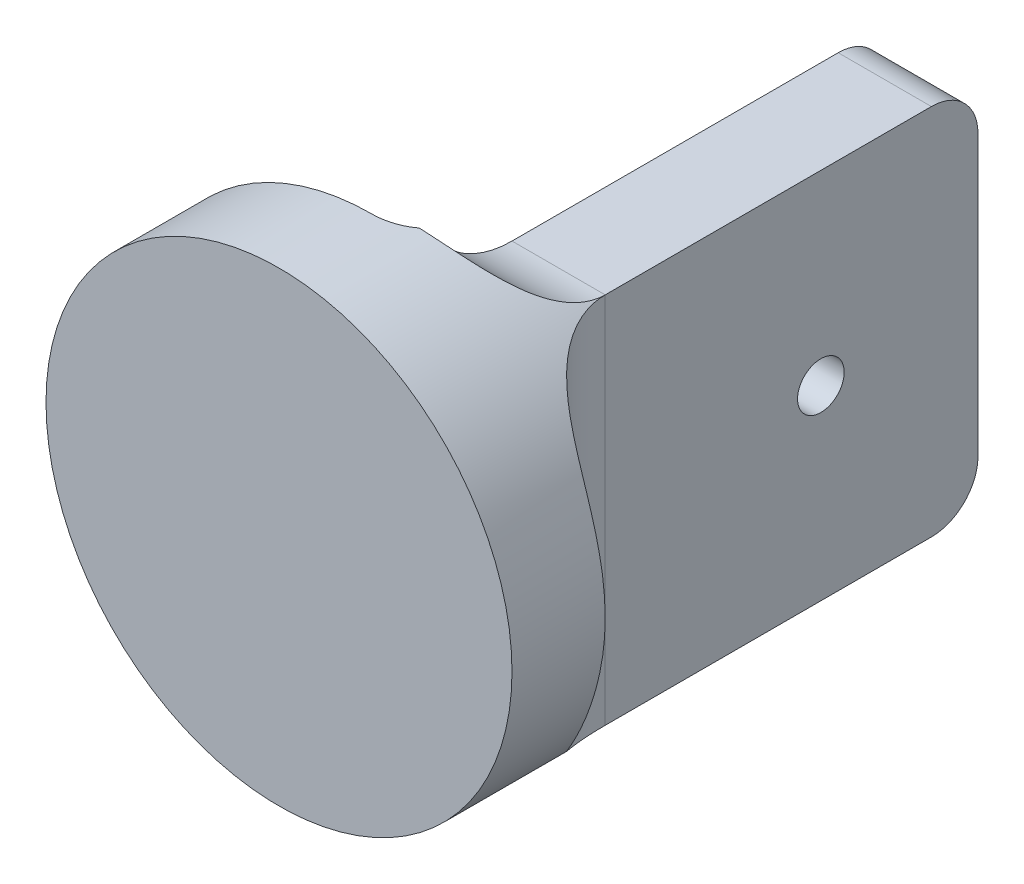
SolidWorks part; units mm, degrees
material "pla filament"
ref_plane "Ön Düzlem" through (0, 0, 0) normal (0, 0, 1) x (1, 0, 0)
ref_plane "Üst Düzlem" through (0, 0, 0) normal (0, 1, 0) x (1, 0, 0)
ref_plane "Sağ Düzlem" through (0, 0, 0) normal (1, 0, 0) x (0, 0, -1)
sketch "Sketch1" plane through (0, 0, 0) normal (0, 0, 1) x (1, 0, 0)
  line L1 (5, -20) -> (15, -20)
  line L2 (5, -20) -> (5, 20)
  line L3 (5, 20) -> (15, 20)
  line L4 (15, -20) -> (15, 20)
  line L5 (5, -20) -> (15, 20) construction
  line L6 (5, 20) -> (15, -20) construction
  circle A0 centre (0, 0) radius 25
  point P3 (10, 0)
  dimension "D1" = 50
  dimension "D2" = 10
  dimension "D3" = 40
extrude "Boss-Extrude1" add sketch "Sketch1" along normal blind 10 contours L3 A0 L1 L2 | L4 A0 | L1 L4 L3 L2 region at (10, 0, 0) region at (-7.2693, 0, 0) region at (19.0776, 0, 0)
sketch "Sketch2" plane through (0, 0, 0) normal (0, 0, -1) x (-1, 0, 0)
  line L4 (-15, -20) -> (-5, -20)
  line L5 (-15, 20) -> (-15, -20)
  line L6 (-5, 20) -> (-15, 20)
  line L7 (-5, -20) -> (-5, 20)
  line L8 (-15, -20) -> (-5, -20)
  line L9 (-15, 20) -> (-15, -20)
  line L10 (-5, 20) -> (-15, 20)
  line L11 (-5, -20) -> (-5, 20)
  circle A1 centre (0, 0) radius 25
  circle A2 centre (0, 0) radius 25
  dimension "D1" = 0
  dimension "D2" = 0
extrude "Boss-Extrude2" add sketch "Sketch2" along normal blind 50 contours L8 L11 L10 L9 region at (10, 0, 0)
fillet "Fillet1" radius 10 1 edges at (15, 0, 0)
fillet "Fillet2" radius 10 2 edges at (10, 20, 0) (10, -20, 0)
fillet "Fillet3" radius 5 3 edges at (10, -20, -50) (10, 20, -50) (5, 0, 0)
sketch "Sketch3" plane through (5, 0, 0) normal (-1, 0, 0) x (0, 0, 1)
  circle A0 centre (-33.1409, 0) radius 2.5
  dimension "D1" = 5
extrude "Cut-Extrude1" cut sketch "Sketch3" against normal blind 50
